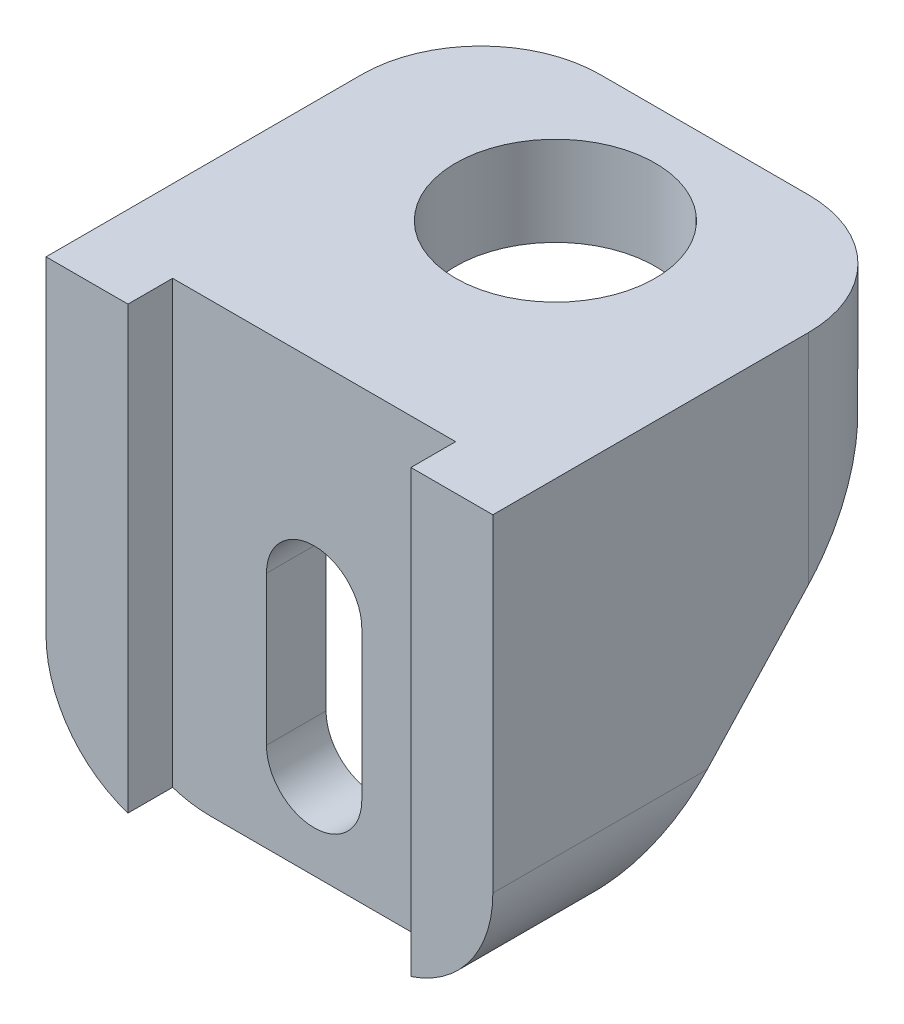
SolidWorks part; units mm, degrees
ref_plane "前视基准面" through (0, 0, 0) normal (0, 0, 1) x (1, 0, 0)
ref_plane "上视基准面" through (0, 0, 0) normal (0, 1, 0) x (1, 0, 0)
ref_plane "右视基准面" through (0, 0, 0) normal (1, 0, 0) x (0, 0, -1)
other "Configuration Table"
sketch "草图1" plane through (0, 0, 0) normal (0, 1, 0) x (1, 0, 0)
  line L0 (0, 5) -> (0, -8.1) construction
  line L1 (-7.5, 5) -> (7.5, 5)
  line L2 (-7.5, 5) -> (-7.5, -8.1)
  line L3 (-7.5, -8.1) -> (7.5, -8.1)
  line L4 (7.5, 5) -> (7.5, -8.1)
  circle A0 centre (0, 0) radius 3.35
  dimension "D1" = 6.7
  dimension "D2" = 8.1
  dimension "D3" = 5
  dimension "D4" = 15
extrude "凸台-拉伸1" add sketch "草图1" along normal blind 3
sketch "草图2" plane through (0, 0, 0) normal (0, -1, 0) x (1, 0, 0)
  line L0 (7.5, 8.1) -> (7.5, -5) construction
  line L1 (-7.5, 8.1) -> (7.5, 8.1)
  line L2 (-7.5, 8.1) -> (-7.5, 6.1)
  line L3 (-7.5, 6.1) -> (7.5, 6.1)
  line L4 (7.5, 8.1) -> (7.5, 6.1)
  dimension "D1" = 2
extrude "凸台-拉伸2" add sketch "草图2" along normal blind 12
sketch "草图3" plane through (0, 3, 0) normal (0, 1, 0) x (1, 0, 0)
  line L0 (0, 0) -> (0, -8.1) construction
  line L1 (-7.5, -8.1) -> (-4.75, -8.1)
  line L2 (-7.5, -8.1) -> (-7.5, -9.6)
  line L3 (-7.5, -9.6) -> (-4.75, -9.6)
  line L4 (-4.75, -8.1) -> (-4.75, -9.6)
  line L9 (-7.5, -8.1) -> (7.5, -8.1) construction
  line L10 (7.5, -9.6) -> (4.75, -9.6)
  line L11 (4.75, -8.1) -> (4.75, -9.6)
  line L12 (7.5, -8.1) -> (4.75, -8.1)
  line L13 (7.5, -8.1) -> (7.5, -9.6)
  dimension "D1" = 4.75
  dimension "D2" = 1.5
extrude "凸台-拉伸3" add sketch "草图3" against normal up to surface (15 mm away) up to face at (0, -12, 7.1)
sketch "草图4" plane through (0, 0, 6.1) normal (0, 0, -1) x (-1, 0, 0)
  line L0 (0, -4) -> (0, -9) construction
  line L1 (1.6, -4) -> (1.6, -9)
  line L2 (-1.6, -4) -> (-1.6, -9)
  line L3 (-7.5, 3) -> (7.5, 3) construction
  line L4 (0, -4) -> (0, -9) construction
  line L5 (3.5, -4) -> (3.5, -9) construction
  line L6 (-3.5, -4) -> (-3.5, -9) construction
  arc A0 (1.6, -4) -> (-1.6, -4) centre (0, -4) ccw
  arc A1 (-1.6, -9) -> (1.6, -9) centre (0, -9) ccw
  arc A2 (3.5, -4) -> (-3.5, -4) centre (0, -4) ccw construction
  arc A3 (-3.5, -9) -> (3.5, -9) centre (0, -9) ccw construction
  point P3 (0, -6.5)
  point P12 (0, -6.5)
  dimension "D1" = 1.6
  dimension "D2" = 7
  dimension "D4" = 3.5
  dimension "D3" = 5
extrude "切除-拉伸1" cut sketch "草图4" against normal up to next
sketch "草图5" plane through (7.5, 0, 0) normal (1, 0, 0) x (0, 0, -1)
  line L0 (-6.1, 0) -> (-6.1, -12)
  line L1 (-6.1, -12) -> (5, 0)
  line L2 (5, 0) -> (-6.1, 0)
extrude "凸台-拉伸4" add sketch "草图5" against normal blind 1
mirror "镜向1" about plane through (0, 0, 0) normal (1, 0, 0) of "凸台-拉伸4"
sketch "草图6" plane through (0, 0, 6.1) normal (0, 0, -1) x (-1, 0, 0)
  circle A0 centre (0, -3.5) radius 3.5
  dimension "D1" = 7
fillet "圆角1" radius 4 4 edges at (-7.5, 1.5, -5) (7.5, 1.5, -5) (-7.5, -12, 7.85) (7.5, -12, 7.85)
fillet "圆角2" radius 2 2 edges at (-6.5, -5.3229, 6.1) (6.5, -5.3229, 6.1)
